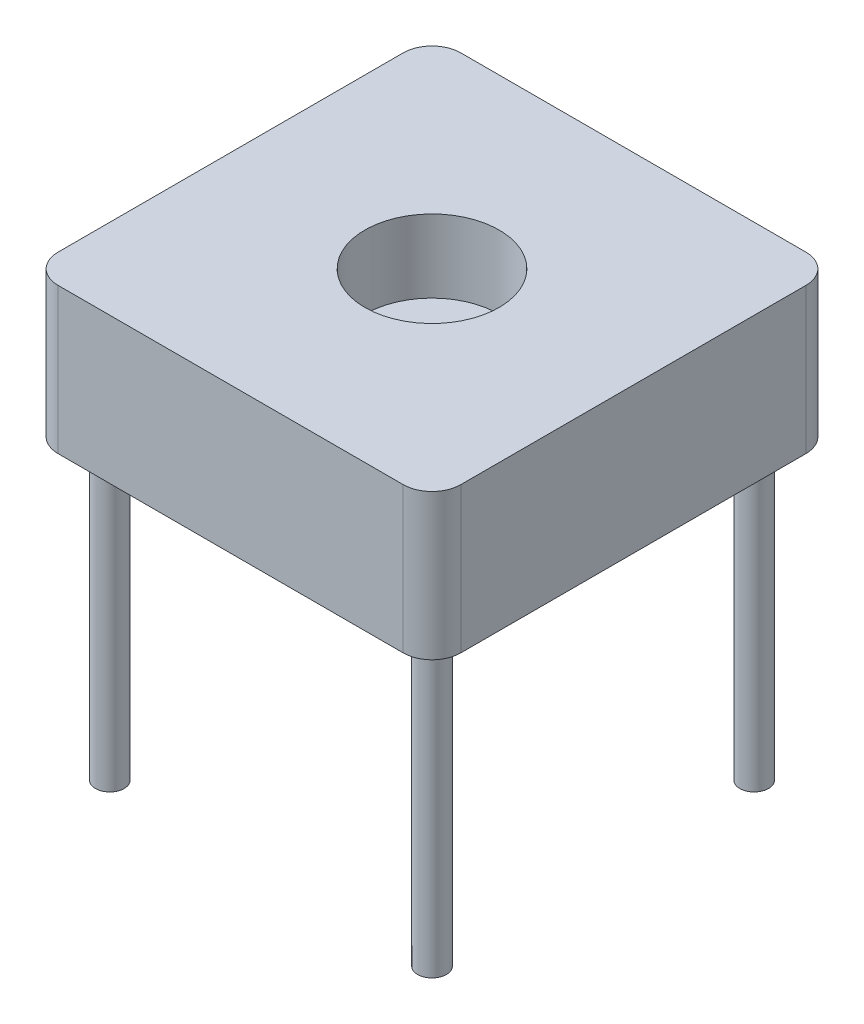
SolidWorks part; units mm, degrees
ref_plane "Front" through (0, 0, 0) normal (0, 0, 1) x (1, 0, 0)
ref_plane "Top" through (0, 0, 0) normal (0, 1, 0) x (1, 0, 0)
ref_plane "Right" through (0, 0, 0) normal (1, 0, 0) x (0, 0, -1)
sketch "Sketch1" plane through (0, 0, 0) normal (0, 1, 0) x (1, 0, 0)
  line L1 (0.75, 0) -> (9.75, 0)
  line L2 (0, 0.75) -> (0, 9.75)
  line L3 (0.75, 10.5) -> (9.75, 10.5)
  line L4 (10.5, 0.75) -> (10.5, 9.75)
  arc A0 (0, 9.75) -> (0.75, 10.5) centre (0.75, 9.75) cw
  arc A1 (9.75, 10.5) -> (10.5, 9.75) centre (9.75, 9.75) cw
  arc A2 (10.5, 0.75) -> (9.75, 0) centre (9.75, 0.75) cw
  arc A3 (0.75, 0) -> (0, 0.75) centre (0.75, 0.75) cw
  point P9 (10.5, 10.5)
  point P12 (10.5, 0)
  point P15 (0, 0)
  dimension "D3" = 0.75
  dimension "D1" = 10.5
  dimension "D2" = 10.5
extrude "Boss-Extrude1" add sketch "Sketch1" along normal blind 3.8
sketch "Sketch2" plane through (0, 3.8, 0) normal (0, 1, 0) x (1, 0, 0)
  circle A0 centre (5.25, 5.25) radius 1.75
  dimension "D3" = 3.5
  dimension "D1" = 5.25
  dimension "D2" = 5.25
extrude "Boss-Extrude2" [suppressed] add sketch "Sketch2" along normal blind 1.8
extrude "Cut-Extrude1" cut sketch "Sketch2<2>" against normal blind 1.9
sketch "Sketch2<2>" plane through (0, 3.8, 0) normal (0, 1, 0) x (1, 0, 0) same geometry as "Sketch2"
sketch "Sketch3" plane through (0, 0, 0) normal (0, -1, 0) x (1, 0, 0)
  line L0 (5.25, 5.1672) -> (5.25, -14.5901) construction
  line L1 (12.0003, -5.25) -> (-1.6331, -5.25) construction
  line L2 (1.05, 0) -> (1.05, -2.625) construction
  line L3 (0, -1.05) -> (2.625, -1.05) construction
  line L4 (0, -9.45) -> (2.625, -9.45) construction
  line L5 (1.05, -7.875) -> (1.05, -10.5) construction
  line L6 (9.45, -10.5) -> (9.45, -7.875) construction
  line L7 (7.875, -9.45) -> (10.5, -9.45) construction
  line L8 (9.45, -2.625) -> (9.45, 0) construction
  line L9 (7.875, -1.05) -> (10.5, -1.05) construction
  line L11 (0, -9.75) -> (0, -0.75) construction
  line L12 (0.75, 0) -> (9.75, 0) construction
  line L13 (9.75, -10.5) -> (0.75, -10.5) construction
  line L14 (10.5, -0.75) -> (10.5, -9.75) construction
  circle A0 centre (9.45, -1.05) radius 0.375
  circle A1 centre (9.45, -9.45) radius 0.375
  circle A2 centre (1.05, -9.45) radius 0.375
  circle A3 centre (1.05, -1.05) radius 0.375
  point P14 (1.05, -9.45)
  point P20 (1.05, -1.05)
  point P22 (9.45, -1.05)
  point P23 (9.45, -9.45)
  dimension "D1" = 5.25
  dimension "D2" = 5.25
  dimension "D15" = 0.75
  dimension "D16" = 0.75
  dimension "D17" = 0.75
  dimension "D18" = 0.75
  dimension "D3" = 2.625
  dimension "D4" = 2.625
  dimension "D5" = 2.625
  dimension "D6" = 2.625
  dimension "D7" = 2.625
  dimension "D8" = 2.625
  dimension "D9" = 2.625
  dimension "D10" = 2.625
  dimension "D11" = 4.2
  dimension "D12" = 4.2
  dimension "D13" = 4.2
  dimension "D14" = 4.2
extrude "Boss-Extrude3" add sketch "Sketch3" along normal blind 7.75
equation "\"len-base\"= 10.5mm"
equation "\"len-half-base\"= \"len-base\" / 2"
equation "\"rad\"= 3.5mm"
equation "\"th-base\"= 3.8mm"
equation "\"D1@Sketch2\"=\"len-half-base\""
equation "\"D2@Sketch2\"=\"len-half-base\""
equation "\"D3@Sketch2\"=\"rad\""
equation "\"D1@Boss-Extrude1\"=\"th-base\""
equation "\"D1@Sketch1\"=\"len-base\""
equation "\"D2@Sketch1\"=\"len-base\""
equation "\"th-button\"= 1.8mm"
equation "\"D1@Boss-Extrude2\"=\"th-button\""
equation "\"D1@Cut-Extrude1\"=\"th-base\"/2"
equation "\"D1@Sketch3\"=\"len-half-base\""
equation "\"D2@Sketch3\"=\"len-half-base\""
equation "\"D3@Sketch3\"=\"len-half-base\"/2"
equation "\"D4@Sketch3\"=\"len-half-base\"/2"
equation "\"D5@Sketch3\"=\"len-half-base\"/2"
equation "\"D6@Sketch3\"=\"len-half-base\"/2"
equation "\"D7@Sketch3\"=\"len-half-base\"/2"
equation "\"D8@Sketch3\"=\"len-half-base\"/2"
equation "\"D9@Sketch3\"=\"len-half-base\"/2"
equation "\"D10@Sketch3\"=\"len-half-base\"/2"
equation "\"D11@Sketch3\"=\"dist-pins\""
equation "\"D12@Sketch3\"=\"D11@Sketch3\""
equation "\"D13@Sketch3\"=\"D11@Sketch3\""
equation "\"D14@Sketch3\"=\"D11@Sketch3\""
equation "\"rad-pins\"= 0.75mm"
equation "\"dist-pins\"= \"len-half-base\" * ( 4 / 5 )"
equation "\"D15@Sketch3\"=\"rad-pins\""
equation "\"D16@Sketch3\"=\"rad-pins\""
equation "\"D17@Sketch3\"=\"rad-pins\""
equation "\"D18@Sketch3\"=\"rad-pins\""
equation "\"len-pins\"= 7.75mm"
equation "\"D1@Boss-Extrude3\"=\"len-pins\""
